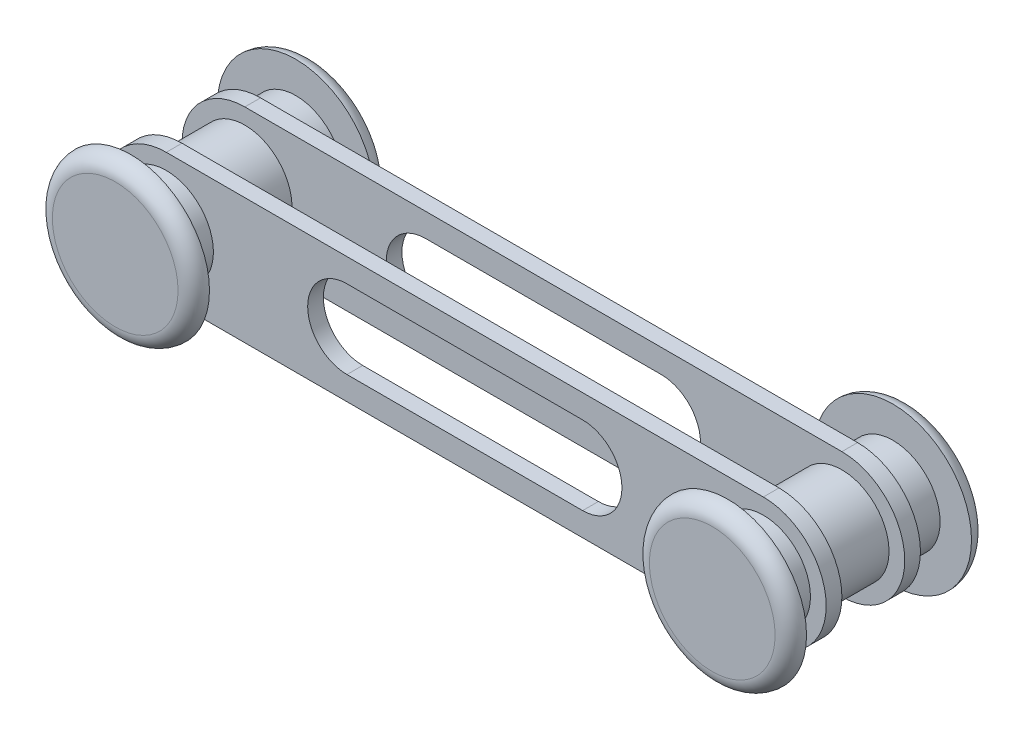
SolidWorks part; units mm, degrees
ref_plane "Front Plane" through (0, 0, 0) normal (0, 0, 1) x (1, 0, 0)
ref_plane "Top Plane" through (0, 0, 0) normal (0, 1, 0) x (1, 0, 0)
ref_plane "Right Plane" through (0, 0, 0) normal (1, 0, 0) x (0, 0, -1)
sketch "Sketch2" plane through (0, 0, 0) normal (0, 0, 1) x (1, 0, 0)
  circle A0 centre (0, 0) radius 30
  dimension "D1" = 60
extrude "Boss-Extrude1" add sketch "Sketch2" along normal mid plane 105
ref_plane "Plane1" through (0, 0, 30) normal (0, 0, 1) x (1, 0, 0)
sketch "Sketch3" plane through (0, 0, 30) normal (0, 0, 1) x (1, 0, 0)
  line L0 (0, -40) -> (0, 40) construction
  line L1 (0, 40) -> (380, 40)
  line L2 (0, 0) -> (380, 0) construction
  line L3 (380, -40) -> (380, 40) construction
  line L4 (0, -40) -> (380, -40)
  arc A0 (0, 40) -> (0, -40) centre (0, 0) ccw
  arc A1 (380, -40) -> (380, 40) centre (380, 0) ccw
  point P6 (0, 0)
  point P7 (0, 0)
  point P12 (380, 0)
  dimension "D1" = 40
  dimension "D2" = 380
extrude "Boss-Extrude2" add sketch "Sketch3" against normal blind 10
sketch "Sketch4" plane through (0, 0, 30) normal (0, 0, 1) x (1, 0, 0)
  line L0 (190, 40) -> (190, -40) construction
  line L1 (380, 40) -> (0, 40) construction
  line L2 (0, -40) -> (380, -40) construction
  line L3 (420, 0) -> (-40, 0) construction
  line L4 (265, 0) -> (115, 0) construction
  line L5 (265, -25) -> (115, -25)
  line L6 (265, 25) -> (115, 25)
  arc A0 (0, 40) -> (0, -40) centre (0, 0) ccw construction
  arc A1 (265, -25) -> (265, 25) centre (265, 0) ccw
  arc A2 (115, 25) -> (115, -25) centre (115, 0) ccw
  point P12 (190, 0)
  point P14 (190, 0)
  dimension "D2" = 25
  dimension "D1" = 150
extrude "Cut-Extrude1" cut sketch "Sketch4" against normal through all
sketch "Sketch5" plane through (0, 0, 0) normal (0, 0, 1) x (1, 0, 0)
  circle A0 centre (380, 0) radius 30
  dimension "D1" = 60
extrude "Boss-Extrude3" add sketch "Sketch5" along normal mid plane 105
mirror "Mirror1" about plane through (0, 0, 0) normal (0, 0, 1) of "Cut-Extrude1", "Boss-Extrude2"
sketch "Sketch6" plane through (0, 0, 52.5) normal (0, 0, 1) x (1, 0, 0)
  circle A0 centre (0, 0) radius 50
  circle A1 centre (380, 0) radius 50
  dimension "D1" = 100
extrude "Boss-Extrude4" add sketch "Sketch6" along normal blind 10
fillet "Fillet1" radius 10 2 edges at (50, 0, 62.5) (430, 0, 62.5)
mirror "Mirror3" about plane through (0, 0, 0) normal (0, 0, 1) of "Boss-Extrude4", "Fillet1"
